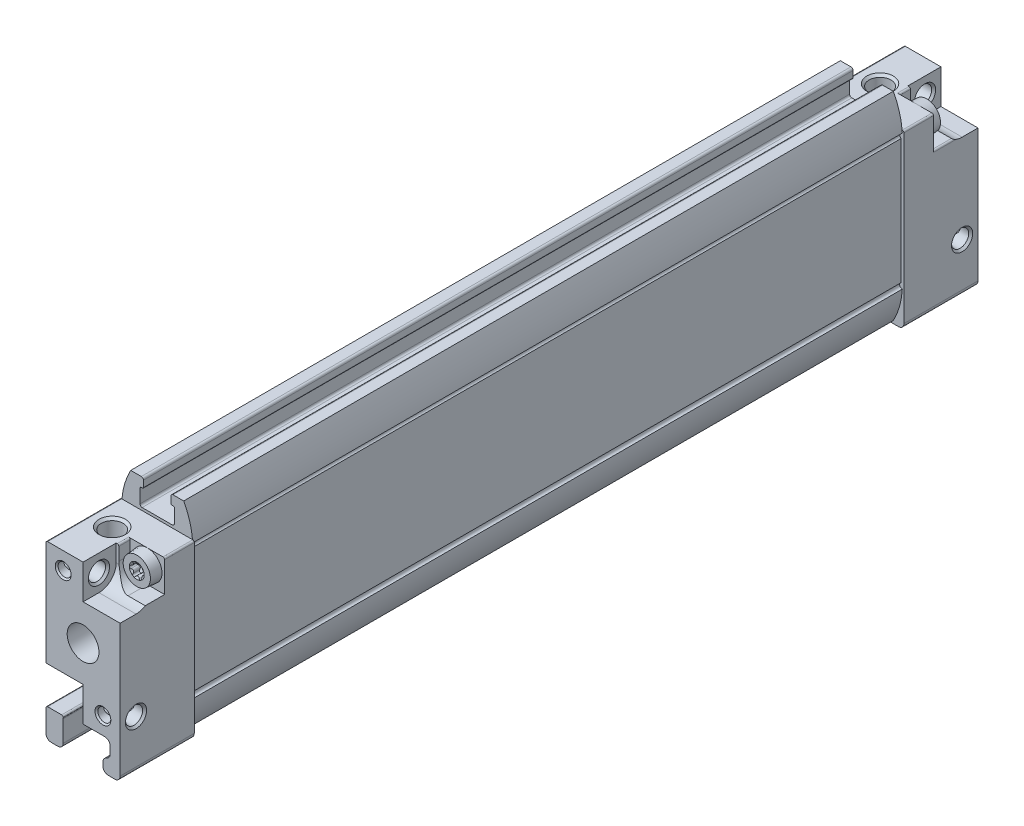
SolidWorks part; units mm, degrees
ref_plane "Front Plane" through (0, 0, 0) normal (0, 0, 1) x (1, 0, 0)
ref_plane "Top Plane" through (0, 0, 0) normal (0, 1, 0) x (1, 0, 0)
ref_plane "Right Plane" through (0, 0, 0) normal (1, 0, 0) x (0, 0, -1)
sketch "Sketch1" plane through (0, 0, 0) normal (0, 0, 1) x (1, 0, 0)
  line L0 (-6, -19.25) -> (-4.75, -19.25)
  line L1 (-3.75, -18.25) -> (-3.75, -14.25)
  line L2 (-2.75, -13.25) -> (4.1, -13.25)
  line L3 (5.1, -14.25) -> (5.1, -15.65)
  line L4 (3.75, -17.5414) -> (3.75, -18.25)
  line L5 (4.75, -19.25) -> (6, -19.25)
  line L6 (7, -18.25) -> (7, 12.95)
  line L7 (6.7, 13.25) -> (-6.7, 13.25)
  line L8 (-7, 12.95) -> (-7, -18.25)
  arc A0 (-7, -18.25) -> (-6, -19.25) centre (-6, -18.25) ccw
  arc A1 (-4.75, -19.25) -> (-3.75, -18.25) centre (-4.75, -18.25) ccw
  arc A2 (-3.75, -14.25) -> (-2.75, -13.25) centre (-2.75, -14.25) cw
  arc A3 (4.1, -13.25) -> (5.1, -14.25) centre (4.1, -14.25) cw
  arc A4 (5.1, -15.65) -> (4.425, -16.5957) centre (4.1, -15.65) cw
  arc A5 (4.425, -16.5957) -> (3.75, -17.5414) centre (4.75, -17.5414) ccw
  arc A6 (3.75, -18.25) -> (4.75, -19.25) centre (4.75, -18.25) ccw
  arc A7 (6, -19.25) -> (7, -18.25) centre (6, -18.25) ccw
  arc A8 (7, 12.95) -> (6.7, 13.25) centre (6.7, 12.95) ccw
  arc A9 (-6.7, 13.25) -> (-7, 12.95) centre (-6.7, 12.95) ccw
extrude "Boss-Extrude1" add sketch "Sketch1" against normal blind 14
ref_plane "Plane1" through (0, 0, -14) normal (0, 0, 1) x (1, 0, 0)
sketch "Sketch2" plane through (0, 0, -14) normal (0, 0, 1) x (1, 0, 0)
  line L0 (-5, -18.75) -> (-3, -18.75)
  line L1 (-2.6, -18.35) -> (-2.6, -17.15)
  line L2 (-2.8, -16.95) -> (-3.05, -16.95)
  line L3 (-3.25, -16.75) -> (-3.25, -14.15)
  line L4 (-2.85, -13.75) -> (2.85, -13.75)
  line L5 (3.25, -14.15) -> (3.25, -16.75)
  line L6 (3.05, -16.95) -> (2.8, -16.95)
  line L7 (2.6, -17.15) -> (2.6, -18.35)
  line L8 (3, -18.75) -> (5, -18.75)
  line L9 (6.5, -11.7917) -> (6.5, 11.7917)
  line L10 (5, 18.75) -> (3, 18.75)
  line L11 (2.6, 18.35) -> (2.6, 17.15)
  line L12 (2.8, 16.95) -> (3.05, 16.95)
  line L13 (3.25, 16.75) -> (3.25, 14.15)
  line L14 (2.85, 13.75) -> (-2.85, 13.75)
  line L15 (-3.25, 14.15) -> (-3.25, 16.75)
  line L16 (-3.05, 16.95) -> (-2.8, 16.95)
  line L17 (-2.6, 17.15) -> (-2.6, 18.35)
  line L18 (-3, 18.75) -> (-5, 18.75)
  line L19 (-6.5, 11.7917) -> (-6.5, -11.7917)
  arc A0 (-6.7, -12.75) -> (-5, -18.75) centre (7.2814, -12.0294) ccw
  arc A1 (-3, -18.75) -> (-2.6, -18.35) centre (-3, -18.35) ccw
  arc A2 (-2.6, -17.15) -> (-2.8, -16.95) centre (-2.8, -17.15) ccw
  arc A3 (-3.05, -16.95) -> (-3.25, -16.75) centre (-3.05, -16.75) cw
  arc A4 (-3.25, -14.15) -> (-2.85, -13.75) centre (-2.85, -14.15) cw
  arc A5 (2.85, -13.75) -> (3.25, -14.15) centre (2.85, -14.15) cw
  arc A6 (3.25, -16.75) -> (3.05, -16.95) centre (3.05, -16.75) cw
  arc A7 (2.8, -16.95) -> (2.6, -17.15) centre (2.8, -17.15) ccw
  arc A8 (2.6, -18.35) -> (3, -18.75) centre (3, -18.35) ccw
  arc A9 (5, -18.75) -> (6.7, -12.75) centre (-7.2814, -12.0294) ccw
  arc A10 (6.7, -12.75) -> (6.5, -11.7917) centre (6.7, -12.25) cw
  arc A11 (6.5, 11.7917) -> (6.7, 12.75) centre (6.7, 12.25) cw
  arc A12 (6.7, 12.75) -> (5, 18.75) centre (-7.2814, 12.0294) ccw
  arc A13 (3, 18.75) -> (2.6, 18.35) centre (3, 18.35) ccw
  arc A14 (2.6, 17.15) -> (2.8, 16.95) centre (2.8, 17.15) ccw
  arc A15 (3.05, 16.95) -> (3.25, 16.75) centre (3.05, 16.75) cw
  arc A16 (3.25, 14.15) -> (2.85, 13.75) centre (2.85, 14.15) cw
  arc A17 (-2.85, 13.75) -> (-3.25, 14.15) centre (-2.85, 14.15) cw
  arc A18 (-3.25, 16.75) -> (-3.05, 16.95) centre (-3.05, 16.75) cw
  arc A19 (-2.8, 16.95) -> (-2.6, 17.15) centre (-2.8, 17.15) ccw
  arc A20 (-2.6, 18.35) -> (-3, 18.75) centre (-3, 18.35) ccw
  arc A21 (-5, 18.75) -> (-6.7, 12.75) centre (7.2814, 12.0294) ccw
  arc A22 (-6.7, 12.75) -> (-6.5, 11.7917) centre (-6.7, 12.25) cw
  arc A23 (-6.5, -11.7917) -> (-6.7, -12.75) centre (-6.7, -12.25) cw
extrude "Boss-Extrude2" add sketch "Sketch2" against normal blind 134
ref_plane "Plane2" through (0, 0, -148) normal (0, 0, 1) x (1, 0, 0)
sketch "Sketch3" plane through (0, 0, -148) normal (0, 0, 1) x (1, 0, 0)
  line L0 (-6, -19.25) -> (-4.75, -19.25)
  line L1 (-3.75, -18.25) -> (-3.75, -14.25)
  line L2 (-2.75, -13.25) -> (4.1, -13.25)
  line L3 (5.1, -14.25) -> (5.1, -15.65)
  line L4 (3.75, -17.5414) -> (3.75, -18.25)
  line L5 (4.75, -19.25) -> (6, -19.25)
  line L6 (7, -18.25) -> (7, 12.95)
  line L7 (6.7, 13.25) -> (-6.7, 13.25)
  line L8 (-7, 12.95) -> (-7, -18.25)
  arc A0 (-7, -18.25) -> (-6, -19.25) centre (-6, -18.25) ccw
  arc A1 (-4.75, -19.25) -> (-3.75, -18.25) centre (-4.75, -18.25) ccw
  arc A2 (-3.75, -14.25) -> (-2.75, -13.25) centre (-2.75, -14.25) cw
  arc A3 (4.1, -13.25) -> (5.1, -14.25) centre (4.1, -14.25) cw
  arc A4 (5.1, -15.65) -> (4.425, -16.5957) centre (4.1, -15.65) cw
  arc A5 (4.425, -16.5957) -> (3.75, -17.5414) centre (4.75, -17.5414) ccw
  arc A6 (3.75, -18.25) -> (4.75, -19.25) centre (4.75, -18.25) ccw
  arc A7 (6, -19.25) -> (7, -18.25) centre (6, -18.25) ccw
  arc A8 (7, 12.95) -> (6.7, 13.25) centre (6.7, 12.95) ccw
  arc A9 (-6.7, 13.25) -> (-7, 12.95) centre (-6.7, 12.95) ccw
extrude "Boss-Extrude3" add sketch "Sketch3" against normal blind 14
sketch "Sketch4" plane through (0, 0, 0) normal (1, 0, 0) x (0, 0, -1)
  line L0 (0, 13.25) -> (0, 6.75)
  line L1 (0, 6.75) -> (3, 6.75)
  line L2 (6.25, 10) -> (6.25, 13.25)
  line L3 (6.25, 13.25) -> (0, 13.25)
  arc A0 (3, 6.75) -> (6.25, 10) centre (3, 10) ccw
extrude "Cut-Extrude1" cut sketch "Sketch4" along normal blind 14
sketch "Sketch5" plane through (0, 0, 0) normal (1, 0, 0) x (0, 0, -1)
  line L0 (159, 6.75) -> (162, 6.75)
  line L1 (162, 6.75) -> (162, 13.25)
  line L2 (162, 13.25) -> (155.75, 13.25)
  line L3 (155.75, 13.25) -> (155.75, 10)
  arc A0 (155.75, 10) -> (159, 6.75) centre (159, 10) ccw
extrude "Cut-Extrude2" cut sketch "Sketch5" along normal blind 14
ref_plane "Plane3" through (0, 0, -3) normal (0, 0, 1) x (1, 0, 0)
sketch "Sketch6" plane through (0, 0, -3) normal (0, 0, 1) x (1, 0, 0)
  line L0 (-7, 10) -> (-7, 12)
  line L1 (-7, 12) -> (-6.621, 11.621)
  line L2 (-6.621, 11.621) -> (-0.379, 11.621)
  line L3 (-0.379, 11.621) -> (0, 12)
  line L4 (0, 12) -> (0, 10)
  line L5 (0, 10) -> (-7, 10)
  line L6 (0, 10) -> (-7, 10) construction
revolve "Cut-Revolve1" cut sketch "Sketch6" angle 360 about L6
cosmetic thread "Cosmetic Thread1" parameters "D1"=7, "D2"=4
ref_plane "Plane4" through (0, 0, -159) normal (0, 0, 1) x (1, 0, 0)
sketch "Sketch7" plane through (0, 0, -159) normal (0, 0, 1) x (1, 0, 0)
  line L0 (-7, 10) -> (-7, 12)
  line L1 (-7, 12) -> (-6.621, 11.621)
  line L2 (-6.621, 11.621) -> (-0.379, 11.621)
  line L3 (-0.379, 11.621) -> (0, 12)
  line L4 (0, 12) -> (0, 10)
  line L5 (0, 10) -> (-7, 10)
  line L6 (0, 10) -> (-7, 10) construction
revolve "Cut-Revolve2" cut sketch "Sketch7" angle 360 about L6
cosmetic thread "Cosmetic Thread2" parameters "D1"=7, "D2"=4
ref_plane "Plane5" through (-3.75, 0, 0) normal (1, 0, 0) x (0, 0, -1)
hole_wizard "Hole1" positions "Sketch9" profile "Sketch8" legacy
sketch "Sketch9" plane through (0, 0, 0) normal (0, 0, 1) x (1, 0, 0)
  point P0 (-3.75, 10)
sketch "Sketch8" plane through (-3.75, 10, 0) normal (1, 0, 0) x (0, -1, 0)
  line L0 (0, 0) -> (0, 5.7099)
  line L1 (0, 5.7099) -> (1.2295, 5)
  line L2 (1.2295, 5) -> (1.2295, 0.2705)
  line L3 (1.2295, 0.2705) -> (1.5, 0)
  line L4 (1.5, 0) -> (0, 0)
  line L5 (0, -14.3089) -> (0, 102.4216) construction
  line L6 (0, 5.7099) -> (-1.2295, 5) construction
  line L7 (-1.2295, 0.2705) -> (-1.5, 0) construction
  dimension "Diameter" = 2.459
  dimension "Depth" = 5
  dimension "C-Sink Diameter" = 3
  dimension "C-Sink Angle" = 90
  dimension "Drill Angle" = 120
cosmetic thread "Cosmetic Thread3" parameters "D1"=4, "D2"=3
hole_wizard "Hole2" positions "Sketch11" profile "Sketch10" legacy
sketch "Sketch11" plane through (0, 0, -162) normal (0, 0, -1) x (-1, 0, 0)
  point P0 (3.75, 10)
sketch "Sketch10" plane through (-3.75, 10, -162) normal (1, 0, 0) x (0, 1, 0)
  line L0 (0, 0) -> (0, 5.7099)
  line L1 (0, 5.7099) -> (1.2295, 5)
  line L2 (1.2295, 5) -> (1.2295, 0.2705)
  line L3 (1.2295, 0.2705) -> (1.5, 0)
  line L4 (1.5, 0) -> (0, 0)
  line L5 (0, -14.3089) -> (0, 102.4216) construction
  line L6 (0, 5.7099) -> (-1.2295, 5) construction
  line L7 (-1.2295, 0.2705) -> (-1.5, 0) construction
  dimension "Diameter" = 2.459
  dimension "Depth" = 5
  dimension "C-Sink Diameter" = 3
  dimension "C-Sink Angle" = 90
  dimension "Drill Angle" = 120
cosmetic thread "Cosmetic Thread4" parameters "D1"=4, "D2"=3
ref_plane "Plane6" through (3.75, 0, 0) normal (1, 0, 0) x (0, 0, -1)
hole_wizard "Hole3" positions "Sketch13" profile "Sketch12" legacy
sketch "Sketch13" plane through (0, 0, 0) normal (0, 0, 1) x (1, 0, 0)
  point P0 (3.75, -10)
sketch "Sketch12" plane through (3.75, -10, 0) normal (1, 0, 0) x (0, -1, 0)
  line L0 (0, 0) -> (0, 5.7099)
  line L1 (0, 5.7099) -> (1.2295, 5)
  line L2 (1.2295, 5) -> (1.2295, 0.2705)
  line L3 (1.2295, 0.2705) -> (1.5, 0)
  line L4 (1.5, 0) -> (0, 0)
  line L5 (0, -14.3089) -> (0, 102.4216) construction
  line L6 (0, 5.7099) -> (-1.2295, 5) construction
  line L7 (-1.2295, 0.2705) -> (-1.5, 0) construction
  dimension "Diameter" = 2.459
  dimension "Depth" = 5
  dimension "C-Sink Diameter" = 3
  dimension "C-Sink Angle" = 90
  dimension "Drill Angle" = 120
cosmetic thread "Cosmetic Thread5" parameters "D1"=4, "D2"=3
hole_wizard "Hole4" positions "Sketch15" profile "Sketch14" legacy
sketch "Sketch15" plane through (0, 0, -162) normal (0, 0, -1) x (-1, 0, 0)
  point P0 (-3.75, -10)
sketch "Sketch14" plane through (3.75, -10, -162) normal (1, 0, 0) x (0, 1, 0)
  line L0 (0, 0) -> (0, 5.7099)
  line L1 (0, 5.7099) -> (1.2295, 5)
  line L2 (1.2295, 5) -> (1.2295, 0.2705)
  line L3 (1.2295, 0.2705) -> (1.5, 0)
  line L4 (1.5, 0) -> (0, 0)
  line L5 (0, -14.3089) -> (0, 102.4216) construction
  line L6 (0, 5.7099) -> (-1.2295, 5) construction
  line L7 (-1.2295, 0.2705) -> (-1.5, 0) construction
  dimension "Diameter" = 2.459
  dimension "Depth" = 5
  dimension "C-Sink Diameter" = 3
  dimension "C-Sink Angle" = 90
  dimension "Drill Angle" = 120
cosmetic thread "Cosmetic Thread6" parameters "D1"=4, "D2"=3
hole_wizard "Hole5" positions "Sketch17" profile "Sketch16" legacy
sketch "Sketch17" plane through (0, 0, -162) normal (0, 0, -1) x (-1, 0, 0)
  point P0 (0, 0)
sketch "Sketch16" plane through (0, 0, -162) normal (1, 0, 0) x (0, 1, 0)
  line L0 (0, 0) -> (0, 7)
  line L1 (0, 7) -> (2, 7)
  line L2 (2, 7) -> (2, 0)
  line L3 (2, 0) -> (0, 0)
  line L4 (0, 110) -> (0, -10) construction
  dimension "Diameter" = 4
  dimension "Depth" = 7
ref_plane "Plane7" through (0, 0, -11) normal (0, 0, 1) x (1, 0, 0)
hole_wizard "Hole6" positions "Sketch19" profile "Sketch18" legacy
sketch "Sketch19" plane through (0, -13.25, 0) normal (0, -1, 0) x (-1, 0, 0)
  point P0 (0, 11)
sketch "Sketch18" plane through (0, -13.25, -11) normal (1, 0, 0) x (0, 0, -1)
  line L0 (0, 0) -> (0, 6.7099)
  line L1 (0, 6.7099) -> (1.2295, 6)
  line L2 (1.2295, 6) -> (1.2295, 0.2705)
  line L3 (1.2295, 0.2705) -> (1.5, 0)
  line L4 (1.5, 0) -> (0, 0)
  line L5 (0, -14.3089) -> (0, 102.4216) construction
  line L6 (0, 6.7099) -> (-1.2295, 6) construction
  line L7 (-1.2295, 0.2705) -> (-1.5, 0) construction
  dimension "Diameter" = 2.459
  dimension "Depth" = 6
  dimension "C-Sink Diameter" = 3
  dimension "C-Sink Angle" = 90
  dimension "Drill Angle" = 120
cosmetic thread "Cosmetic Thread7" parameters "D1"=4, "D2"=3
ref_plane "Plane8" through (0, 0, -151) normal (0, 0, 1) x (1, 0, 0)
hole_wizard "Hole7" positions "Sketch21" profile "Sketch20" legacy
sketch "Sketch21" plane through (0, -13.25, 0) normal (0, -1, 0) x (-1, 0, 0)
  point P0 (0, 151)
sketch "Sketch20" plane through (0, -13.25, -151) normal (1, 0, 0) x (0, 0, -1)
  line L0 (0, 0) -> (0, 6.7099)
  line L1 (0, 6.7099) -> (1.2295, 6)
  line L2 (1.2295, 6) -> (1.2295, 0.2705)
  line L3 (1.2295, 0.2705) -> (1.5, 0)
  line L4 (1.5, 0) -> (0, 0)
  line L5 (0, -14.3089) -> (0, 102.4216) construction
  line L6 (0, 6.7099) -> (-1.2295, 6) construction
  line L7 (-1.2295, 0.2705) -> (-1.5, 0) construction
  dimension "Diameter" = 2.459
  dimension "Depth" = 6
  dimension "C-Sink Diameter" = 3
  dimension "C-Sink Angle" = 90
  dimension "Drill Angle" = 120
cosmetic thread "Cosmetic Thread8" parameters "D1"=4, "D2"=3
ref_plane "Plane9" through (-3, 0, 0) normal (1, 0, 0) x (0, 0, -1)
hole_wizard "Hole8" positions "Sketch23" profile "Sketch22" legacy
sketch "Sketch23" plane through (0, 13.25, 0) normal (0, 1, 0) x (1, 0, 0)
  point P0 (-3, 8.5)
sketch "Sketch22" plane through (-3, 13.25, -8.5) normal (1, 0, 0) x (0, 0, 1)
  line L0 (0, 0) -> (0, 9.1934)
  line L1 (0, 9.1934) -> (2.067, 8)
  line L2 (2.067, 8) -> (2.067, 0.433)
  line L3 (2.067, 0.433) -> (2.5, 0)
  line L4 (2.5, 0) -> (0, 0)
  line L5 (0, -14.3089) -> (0, 102.4216) construction
  line L6 (0, 9.1934) -> (-2.067, 8) construction
  line L7 (-2.067, 0.433) -> (-2.5, 0) construction
  dimension "Diameter" = 4.134
  dimension "Depth" = 8
  dimension "C-Sink Diameter" = 5
  dimension "C-Sink Angle" = 90
  dimension "Drill Angle" = 120
cosmetic thread "Cosmetic Thread9" parameters "D1"=5, "D2"=5
hole_wizard "Hole9" positions "Sketch25" profile "Sketch24" legacy
sketch "Sketch25" plane through (0, 13.25, 0) normal (0, 1, 0) x (1, 0, 0)
  point P0 (-3, 153.5)
sketch "Sketch24" plane through (-3, 13.25, -153.5) normal (1, 0, 0) x (0, 0, 1)
  line L0 (0, 0) -> (0, 8.1934)
  line L1 (0, 8.1934) -> (2.067, 7)
  line L2 (2.067, 7) -> (2.067, 0.433)
  line L3 (2.067, 0.433) -> (2.5, 0)
  line L4 (2.5, 0) -> (0, 0)
  line L5 (0, -14.3089) -> (0, 102.4216) construction
  line L6 (0, 8.1934) -> (-2.067, 7) construction
  line L7 (-2.067, 0.433) -> (-2.5, 0) construction
  dimension "Diameter" = 4.134
  dimension "Depth" = 7
  dimension "C-Sink Diameter" = 5
  dimension "C-Sink Angle" = 90
  dimension "Drill Angle" = 120
cosmetic thread "Cosmetic Thread10" parameters "D1"=5, "D2"=5
ref_plane "Plane10" through (0, 0, -138.15) normal (0, 0, 1) x (1, 0, 0)
sketch "Sketch26" plane through (0, 0, -138.15) normal (0, 0, 1) x (1, 0, 0)
  line L0 (4.5, -4.5) -> (4.5, 4.5)
  line L1 (-4.5, 4.5) -> (-4.5, -4.5)
  arc A0 (-4.5, -4.5) -> (0, -9) centre (0, -4.5) ccw
  arc A1 (0, -9) -> (4.5, -4.5) centre (0, -4.5) ccw
  arc A2 (4.5, 4.5) -> (0, 9) centre (0, 4.5) ccw
  arc A3 (0, 9) -> (-4.5, 4.5) centre (0, 4.5) ccw
sketch "Sketch27" plane through (0, 0, 0) normal (1, 0, 0) x (0, 0, -1)
  line L0 (0, 0) -> (0, 3)
  line L1 (0, 3) -> (30.5, 3)
  line L2 (30.5, 3) -> (30.5, 0)
  line L3 (30.5, 0) -> (0, 0)
  line L4 (30.5, 0) -> (0, 0) construction
revolve "Cut-Revolve3" cut sketch "Sketch27" angle 360 about L4 reverse direction yes
extrude "Cut-Extrude3" cut sketch "Sketch26" along normal blind 114.3
sketch "Sketch28" plane through (0, 0, 0) normal (1, 0, 0) x (0, 0, -1)
  line L0 (-1, -6.75) -> (-1, -13.25)
  line L1 (-1, -13.25) -> (3, -13.25)
  line L2 (3, -6.75) -> (-1, -6.75)
  arc A0 (3, -13.25) -> (3, -6.75) centre (3, -10) ccw
extrude "Cut-Extrude4" cut sketch "Sketch28" against normal blind 14
sketch "Sketch29" plane through (0, 0, -3) normal (0, 0, 1) x (1, 0, 0)
  line L0 (0, -10) -> (0, -8)
  line L1 (0, -8) -> (0.379, -8.379)
  line L2 (0.379, -8.379) -> (6.621, -8.379)
  line L3 (6.621, -8.379) -> (7, -8)
  line L4 (7, -8) -> (7, -10)
  line L5 (7, -10) -> (0, -10)
  line L6 (7, -10) -> (0, -10) construction
revolve "Cut-Revolve4" cut sketch "Sketch29" angle 360 about L6 reverse direction yes
cosmetic thread "Cosmetic Thread11" parameters "D1"=7, "D2"=4
sketch "Sketch30" plane through (0, 0, 0) normal (1, 0, 0) x (0, 0, -1)
  line L0 (159, -13.25) -> (163, -13.25)
  line L1 (163, -13.25) -> (163, -6.75)
  line L2 (163, -6.75) -> (159, -6.75)
  arc A0 (159, -6.75) -> (159, -13.25) centre (159, -10) ccw
extrude "Cut-Extrude5" cut sketch "Sketch30" against normal blind 14
sketch "Sketch31" plane through (0, 0, -159) normal (0, 0, 1) x (1, 0, 0)
  line L0 (0, -10) -> (0, -8)
  line L1 (0, -8) -> (0.379, -8.379)
  line L2 (0.379, -8.379) -> (6.621, -8.379)
  line L3 (6.621, -8.379) -> (7, -8)
  line L4 (7, -8) -> (7, -10)
  line L5 (7, -10) -> (0, -10)
  line L6 (7, -10) -> (0, -10) construction
revolve "Cut-Revolve5" cut sketch "Sketch31" angle 360 about L6 reverse direction yes
cosmetic thread "Cosmetic Thread12" parameters "D1"=7, "D2"=4
ref_plane "Plane11" through (2.5, 0, 0) normal (1, 0, 0) x (0, 0, -1)
ref_plane "Plane12" through (-2.5, 0, 0) normal (1, 0, 0) x (0, 0, -1)
hole_wizard "Hole10" positions "Sketch33" profile "Sketch32" legacy
sketch "Sketch33" plane through (0, 0, -162) normal (0, 0, -1) x (-1, 0, 0)
  point P0 (-2.5, -4.75)
sketch "Sketch32" plane through (2.5, -4.75, -162) normal (1, 0, 0) x (0, 1, 0)
  line L0 (0, 0) -> (0, 5)
  line L1 (0, 5) -> (2.067, 5)
  line L2 (2.067, 5) -> (2.067, 0.433)
  line L3 (2.067, 0.433) -> (2.5, 0)
  line L4 (2.5, 0) -> (0, 0)
  line L5 (0, -6.4453) -> (0, 115.525) construction
  line L6 (-2.067, 0.433) -> (-2.5, 0) construction
  dimension "Diameter" = 4.134
  dimension "Depth" = 5
  dimension "C-Sink Angle" = 90
  dimension "C-Sink Diameter" = 5
cosmetic thread "Cosmetic Thread13" parameters "D1"=5, "D2"=5
hole_wizard "Hole11" positions "Sketch35" profile "Sketch34" legacy
sketch "Sketch35" plane through (0, 0, -162) normal (0, 0, -1) x (-1, 0, 0)
  point P0 (2.5, 4.75)
sketch "Sketch34" plane through (-2.5, 4.75, -162) normal (1, 0, 0) x (0, 1, 0)
  line L0 (0, 0) -> (0, 5)
  line L1 (0, 5) -> (2.067, 5)
  line L2 (2.067, 5) -> (2.067, 0.433)
  line L3 (2.067, 0.433) -> (2.5, 0)
  line L4 (2.5, 0) -> (0, 0)
  line L5 (0, -6.4453) -> (0, 115.525) construction
  line L6 (-2.067, 0.433) -> (-2.5, 0) construction
  dimension "Diameter" = 4.134
  dimension "Depth" = 5
  dimension "C-Sink Angle" = 90
  dimension "C-Sink Diameter" = 5
cosmetic thread "Cosmetic Thread14" parameters "D1"=5, "D2"=5
ref_plane "Plane13" through (0, 0, -8.4) normal (0, 0, 1) x (1, 0, 0)
sketch "Sketch36" plane through (0, 0, -8.4) normal (0, 0, 1) x (1, 0, 0)
  line L0 (0.5, 12.95) -> (0.5, 10.5)
  line L1 (3.75, 7.25) -> (7, 7.25)
  line L2 (7, 7.25) -> (7, 14.25)
  line L3 (7, 14.25) -> (0.2, 14.25)
  line L4 (0.2, 14.25) -> (0.2, 13.25)
  arc A0 (0.2, 13.25) -> (0.5, 12.95) centre (0.2, 12.95) cw
  arc A1 (0.5, 10.5) -> (3.75, 7.25) centre (3.75, 10.5) ccw
extrude "Cut-Extrude6" cut sketch "Sketch36" along normal blind 8.5
sketch "Sketch37" plane through (0, 0, -8.4) normal (0, 0, 1) x (1, 0, 0)
  line L0 (-8, -14.05) -> (-7, -14.05)
  line L1 (-6.7, -13.75) -> (-4.05, -13.75)
  line L2 (-3.75, -14.05) -> (-0.0902, -14.05)
  line L3 (-0.0902, -14.05) -> (-1.3977, -12.7425)
  line L4 (-3.75, -7.25) -> (-8, -7.25)
  line L5 (-8, -7.25) -> (-8, -14.05)
  arc A0 (-7, -14.05) -> (-6.7, -13.75) centre (-6.7, -14.05) cw
  arc A1 (-4.05, -13.75) -> (-3.75, -14.05) centre (-4.05, -14.05) cw
  arc A2 (-1.3977, -12.7425) -> (-3.75, -7.25) centre (-3.75, -10.5) ccw
extrude "Cut-Extrude7" cut sketch "Sketch37" along normal blind 8.5
ref_plane "Plane14" through (0, 0, -153.6) normal (0, 0, 1) x (1, 0, 0)
sketch "Sketch38" plane through (0, 0, -153.6) normal (0, 0, 1) x (1, 0, 0)
  line L0 (0.5, 12.95) -> (0.5, 10.5)
  line L1 (3.75, 7.25) -> (6.7, 7.25)
  line L2 (7, 6.95) -> (8, 6.95)
  line L3 (8, 6.95) -> (8, 14.25)
  line L4 (8, 14.25) -> (0.2, 14.25)
  line L5 (0.2, 14.25) -> (0.2, 13.25)
  arc A0 (0.2, 13.25) -> (0.5, 12.95) centre (0.2, 12.95) cw
  arc A1 (0.5, 10.5) -> (3.75, 7.25) centre (3.75, 10.5) ccw
  arc A2 (6.7, 7.25) -> (7, 6.95) centre (6.7, 6.95) cw
extrude "Cut-Extrude8" cut sketch "Sketch38" against normal blind 8.5
sketch "Sketch39" plane through (0, 0, -153.6) normal (0, 0, 1) x (1, 0, 0)
  line L0 (-8, -6.95) -> (-8, -14.05)
  line L1 (-8, -14.05) -> (-7, -14.05)
  line L2 (-6.7, -13.75) -> (-4.05, -13.75)
  line L3 (-3.75, -14.05) -> (-0.0902, -14.05)
  line L4 (-0.0902, -14.05) -> (-1.3977, -12.7425)
  line L5 (-3.75, -7.25) -> (-6.7, -7.25)
  line L6 (-7, -6.95) -> (-8, -6.95)
  arc A0 (-7, -14.05) -> (-6.7, -13.75) centre (-6.7, -14.05) cw
  arc A1 (-4.05, -13.75) -> (-3.75, -14.05) centre (-4.05, -14.05) cw
  arc A2 (-1.3977, -12.7425) -> (-3.75, -7.25) centre (-3.75, -10.5) ccw
  arc A3 (-6.7, -7.25) -> (-7, -6.95) centre (-6.7, -6.95) cw
extrude "Cut-Extrude9" cut sketch "Sketch39" against normal blind 8.5
ref_plane "Plane15" through (0, 0, -162) normal (0, 0, 1) x (1, 0, 0)
sketch "Sketch40" plane through (3.75, 0, 0) normal (1, 0, 0) x (0, 0, -1)
  line L0 (7.2083, 10.5) -> (6.4, 11.9)
  line L1 (6.4, 11.9) -> (6.4, 13.075)
  line L2 (6.4, 13.075) -> (8.4, 13.25)
  line L3 (8.4, 13.25) -> (8.4, 10.5)
  line L4 (8.4, 10.5) -> (7.2083, 10.5)
  line L5 (8.4, 10.5) -> (7.2083, 10.5) construction
revolve "Revolve1" add sketch "Sketch40" angle 360 about L5 reverse direction yes
sketch "Sketch41" plane through (-3.75, 0, 0) normal (1, 0, 0) x (0, 0, -1)
  line L0 (7.2083, -10.5) -> (6.4, -9.1)
  line L1 (6.4, -9.1) -> (6.4, -7.925)
  line L2 (6.4, -7.925) -> (8.4, -7.75)
  line L3 (8.4, -7.75) -> (8.4, -10.5)
  line L4 (8.4, -10.5) -> (7.2083, -10.5)
  line L5 (8.4, -10.5) -> (7.2083, -10.5) construction
revolve "Revolve2" add sketch "Sketch41" angle 360 about L5 reverse direction yes
sketch "Sketch42" plane through (3.75, 0, 0) normal (1, 0, 0) x (0, 0, -1)
  line L0 (153.6, 10.5) -> (153.6, 13.25)
  line L1 (153.6, 13.25) -> (155.6, 13.075)
  line L2 (155.6, 13.075) -> (155.6, 11.9)
  line L3 (155.6, 11.9) -> (154.7917, 10.5)
  line L4 (154.7917, 10.5) -> (153.6, 10.5)
  line L5 (154.7917, 10.5) -> (153.6, 10.5) construction
revolve "Revolve3" add sketch "Sketch42" angle 360 about L5 reverse direction yes
sketch "Sketch43" plane through (-3.75, 0, 0) normal (1, 0, 0) x (0, 0, -1)
  line L0 (153.6, -10.5) -> (153.6, -7.75)
  line L1 (153.6, -7.75) -> (155.6, -7.925)
  line L2 (155.6, -7.925) -> (155.6, -9.1)
  line L3 (155.6, -9.1) -> (154.7917, -10.5)
  line L4 (154.7917, -10.5) -> (153.6, -10.5)
  line L5 (154.7917, -10.5) -> (153.6, -10.5) construction
revolve "Revolve4" add sketch "Sketch43" angle 360 about L5 reverse direction yes
ref_plane "Plane16" through (0, 0, -6.4) normal (0, 0, 1) x (1, 0, 0)
ref_plane "Plane17" through (0, 0, -155.6) normal (0, 0, 1) x (1, 0, 0)
sketch "Sketch44" plane through (0, 0, -6.4) normal (0, 0, 1) x (1, 0, 0)
  arc A0 (2.5654, 10.7724) -> (2.5654, 10.2276) centre (2.63, 10.5) ccw
  arc A1 (2.5654, 10.2276) -> (2.9218, 9.6103) centre (2.4523, 9.7508) cw
  arc A2 (2.9218, 9.6103) -> (3.3936, 9.3379) centre (3.19, 9.5301) ccw
  arc A3 (3.3936, 9.3379) -> (4.1064, 9.3379) centre (3.75, 9.0016) cw
  arc A4 (4.1064, 9.3379) -> (4.5782, 9.6103) centre (4.31, 9.5301) ccw
  arc A5 (4.5782, 9.6103) -> (4.9346, 10.2276) centre (5.0477, 9.7508) cw
  arc A6 (4.9346, 10.2276) -> (4.9346, 10.7724) centre (4.87, 10.5) ccw
  arc A7 (4.9346, 10.7724) -> (4.5782, 11.3897) centre (5.0477, 11.2492) cw
  arc A8 (4.5782, 11.3897) -> (4.1064, 11.6621) centre (4.31, 11.4699) ccw
  arc A9 (4.1064, 11.6621) -> (3.3936, 11.6621) centre (3.75, 11.9984) cw
  arc A10 (3.3936, 11.6621) -> (2.9218, 11.3897) centre (3.19, 11.4699) ccw
  arc A11 (2.9218, 11.3897) -> (2.5654, 10.7724) centre (2.4523, 11.2492) cw
extrude "Cut-Extrude10" cut sketch "Sketch44" against normal blind 2.2
sketch "Sketch45" plane through (0, 0, -6.4) normal (0, 0, 1) x (1, 0, 0)
  arc A0 (-4.9346, -10.2276) -> (-4.9346, -10.7724) centre (-4.87, -10.5) ccw
  arc A1 (-4.9346, -10.7724) -> (-4.5782, -11.3897) centre (-5.0477, -11.2492) cw
  arc A2 (-4.5782, -11.3897) -> (-4.1064, -11.6621) centre (-4.31, -11.4699) ccw
  arc A3 (-4.1064, -11.6621) -> (-3.3936, -11.6621) centre (-3.75, -11.9984) cw
  arc A4 (-3.3936, -11.6621) -> (-2.9218, -11.3897) centre (-3.19, -11.4699) ccw
  arc A5 (-2.9218, -11.3897) -> (-2.5654, -10.7724) centre (-2.4523, -11.2492) cw
  arc A6 (-2.5654, -10.7724) -> (-2.5654, -10.2276) centre (-2.63, -10.5) ccw
  arc A7 (-2.5654, -10.2276) -> (-2.9218, -9.6103) centre (-2.4523, -9.7508) cw
  arc A8 (-2.9218, -9.6103) -> (-3.3936, -9.3379) centre (-3.19, -9.5301) ccw
  arc A9 (-3.3936, -9.3379) -> (-4.1064, -9.3379) centre (-3.75, -9.0016) cw
  arc A10 (-4.1064, -9.3379) -> (-4.5782, -9.6103) centre (-4.31, -9.5301) ccw
  arc A11 (-4.5782, -9.6103) -> (-4.9346, -10.2276) centre (-5.0477, -9.7508) cw
extrude "Cut-Extrude11" cut sketch "Sketch45" against normal blind 2.2
sketch "Sketch46" plane through (0, 0, -155.6) normal (0, 0, 1) x (1, 0, 0)
  arc A0 (2.5654, 10.7724) -> (2.5654, 10.2276) centre (2.63, 10.5) ccw
  arc A1 (2.5654, 10.2276) -> (2.9218, 9.6103) centre (2.4523, 9.7508) cw
  arc A2 (2.9218, 9.6103) -> (3.3936, 9.3379) centre (3.19, 9.5301) ccw
  arc A3 (3.3936, 9.3379) -> (4.1064, 9.3379) centre (3.75, 9.0016) cw
  arc A4 (4.1064, 9.3379) -> (4.5782, 9.6103) centre (4.31, 9.5301) ccw
  arc A5 (4.5782, 9.6103) -> (4.9346, 10.2276) centre (5.0477, 9.7508) cw
  arc A6 (4.9346, 10.2276) -> (4.9346, 10.7724) centre (4.87, 10.5) ccw
  arc A7 (4.9346, 10.7724) -> (4.5782, 11.3897) centre (5.0477, 11.2492) cw
  arc A8 (4.5782, 11.3897) -> (4.1064, 11.6621) centre (4.31, 11.4699) ccw
  arc A9 (4.1064, 11.6621) -> (3.3936, 11.6621) centre (3.75, 11.9984) cw
  arc A10 (3.3936, 11.6621) -> (2.9218, 11.3897) centre (3.19, 11.4699) ccw
  arc A11 (2.9218, 11.3897) -> (2.5654, 10.7724) centre (2.4523, 11.2492) cw
extrude "Cut-Extrude12" cut sketch "Sketch46" along normal blind 2.2
sketch "Sketch47" plane through (0, 0, -155.6) normal (0, 0, 1) x (1, 0, 0)
  arc A0 (-4.9346, -10.2276) -> (-4.9346, -10.7724) centre (-4.87, -10.5) ccw
  arc A1 (-4.9346, -10.7724) -> (-4.5782, -11.3897) centre (-5.0477, -11.2492) cw
  arc A2 (-4.5782, -11.3897) -> (-4.1064, -11.6621) centre (-4.31, -11.4699) ccw
  arc A3 (-4.1064, -11.6621) -> (-3.3936, -11.6621) centre (-3.75, -11.9984) cw
  arc A4 (-3.3936, -11.6621) -> (-2.9218, -11.3897) centre (-3.19, -11.4699) ccw
  arc A5 (-2.9218, -11.3897) -> (-2.5654, -10.7724) centre (-2.4523, -11.2492) cw
  arc A6 (-2.5654, -10.7724) -> (-2.5654, -10.2276) centre (-2.63, -10.5) ccw
  arc A7 (-2.5654, -10.2276) -> (-2.9218, -9.6103) centre (-2.4523, -9.7508) cw
  arc A8 (-2.9218, -9.6103) -> (-3.3936, -9.3379) centre (-3.19, -9.5301) ccw
  arc A9 (-3.3936, -9.3379) -> (-4.1064, -9.3379) centre (-3.75, -9.0016) cw
  arc A10 (-4.1064, -9.3379) -> (-4.5782, -9.6103) centre (-4.31, -9.5301) ccw
  arc A11 (-4.5782, -9.6103) -> (-4.9346, -10.2276) centre (-5.0477, -9.7508) cw
extrude "Cut-Extrude13" cut sketch "Sketch47" along normal blind 2.2
ref_plane "Plane18" through (0, 0, -152) normal (0, 0, 1) x (1, 0, 0)
sketch "Sketch48" plane through (3.75, 0, 0) normal (1, 0, 0) x (0, 0, -1)
  line L0 (8.4783, 10.5) -> (7.67, 11.9)
  line L1 (7.67, 11.9) -> (8.6, 11.9)
  line L2 (8.6, 11.9) -> (8.6, 10.5)
  line L3 (8.6, 10.5) -> (8.4783, 10.5)
  line L4 (8.6, 10.5) -> (8.4783, 10.5) construction
revolve "Revolve5" add sketch "Sketch48" angle 360 about L4 reverse direction yes
sketch "Sketch49" plane through (3.75, 0, 0) normal (1, 0, 0) x (0, 0, -1)
  line L0 (153.4, 10.5) -> (153.4, 11.9)
  line L1 (153.4, 11.9) -> (154.33, 11.9)
  line L2 (154.33, 11.9) -> (153.5217, 10.5)
  line L3 (153.5217, 10.5) -> (153.4, 10.5)
  line L4 (153.5217, 10.5) -> (153.4, 10.5) construction
revolve "Revolve6" add sketch "Sketch49" angle 360 about L4 reverse direction yes
sketch "Sketch50" plane through (-3.75, 0, 0) normal (1, 0, 0) x (0, 0, -1)
  line L0 (8.4783, -10.5) -> (7.67, -9.1)
  line L1 (7.67, -9.1) -> (8.6, -9.1)
  line L2 (8.6, -9.1) -> (8.6, -10.5)
  line L3 (8.6, -10.5) -> (8.4783, -10.5)
  line L4 (8.6, -10.5) -> (8.4783, -10.5) construction
revolve "Revolve7" add sketch "Sketch50" angle 360 about L4 reverse direction yes
sketch "Sketch51" plane through (-3.75, 0, 0) normal (1, 0, 0) x (0, 0, -1)
  line L0 (153.4, -10.5) -> (153.4, -9.1)
  line L1 (153.4, -9.1) -> (154.33, -9.1)
  line L2 (154.33, -9.1) -> (153.5217, -10.5)
  line L3 (153.5217, -10.5) -> (153.4, -10.5)
  line L4 (153.5217, -10.5) -> (153.4, -10.5) construction
revolve "Revolve8" add sketch "Sketch51" angle 360 about L4 reverse direction yes
ref_plane "ANBAU XY" through (0, 0, 0) normal (0, 0, -1) x (-1, 0, 0)
ref_plane "ANBAU XZ" through (0, 0, 0) normal (0, 1, 0) x (1, 0, 0)
ref_plane "ANBAU YZ" through (0, 0, 0) normal (1, 0, 0) x (0, 0, -1)
ref_axis "ANBAU X" through (-80.9, 0, 0) along (1, 0, 0)
ref_axis "ANBAU Y" through (0, 50, 0) along (0, -1, 0)
ref_axis "ANBAU Z" through (0, 0, -80.9) along (0, 0, 1)
sketch3d "ANBAU"
  point P0 (0, 0, 0)
ref_plane "PLUG 1 XY" through (0, 0, -162) normal (0, 0, 1) x (1, 0, 0)
ref_plane "PLUG 1 XZ" through (0, 4.75, 0) normal (0, -1, 0) x (-1, 0, 0)
ref_plane "PLUG 1 YZ" through (-2.5, 0, 0) normal (1, 0, 0) x (0, 0, -1)
ref_axis "PLUG 1 X" through (-80.9, 4.75, -162) along (1, 0, 0)
ref_axis "PLUG 1 Y" through (-2.5, -50, -162) along (0, 1, 0)
ref_axis "PLUG 1 Z" through (-2.5, 4.75, 80.9) along (0, 0, -1)
sketch3d "PLUG 1"
  point P0 (-2.5, 4.75, -162)
ref_plane "PLUG 2 XY" through (0, 0, -162) normal (0, 0, 1) x (1, 0, 0)
ref_plane "PLUG 2 XZ" through (0, -4.75, 0) normal (0, -1, 0) x (-1, 0, 0)
ref_plane "PLUG 2 YZ" through (2.5, 0, 0) normal (1, 0, 0) x (0, 0, -1)
ref_axis "PLUG 2 X" through (-80.9, -4.75, -162) along (1, 0, 0)
ref_axis "PLUG 2 Y" through (2.5, -50, -162) along (0, 1, 0)
ref_axis "PLUG 2 Z" through (2.5, -4.75, 80.9) along (0, 0, -1)
sketch3d "PLUG 2"
  point P0 (2.5, -4.75, -162)
ref_plane "zylinder XY" through (0, 0, -138.15) normal (0, 0, 1) x (1, 0, 0)
ref_plane "zylinder XZ" through (0, 0, 0) normal (0, -1, 0) x (-1, 0, 0)
ref_plane "zylinder YZ" through (0, 0, 0) normal (1, 0, 0) x (0, 0, -1)
ref_axis "zylinder X" through (-80.9, 0, -138.15) along (1, 0, 0)
ref_axis "zylinder Y" through (0, -50, -138.15) along (0, 1, 0)
ref_axis "zylinder Z" through (0, 0, 80.9) along (0, 0, -1)
sketch3d "zylinder"
  point P0 (0, 0, -138.15)
